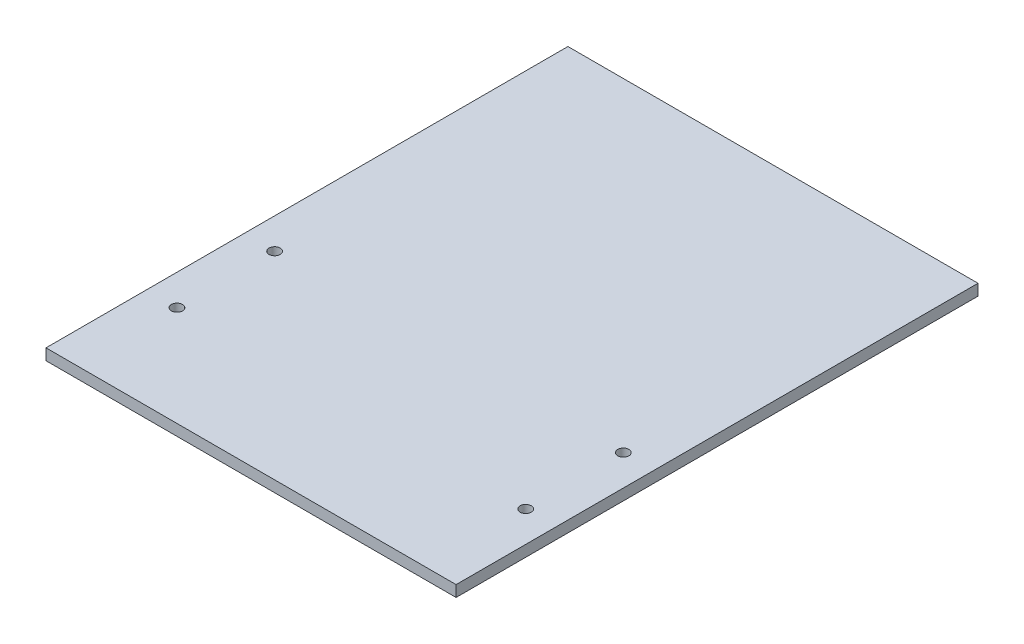
SolidWorks part; units mm, degrees
ref_plane "Front Plane" through (0, 0, 0) normal (0, 0, 1) x (1, 0, 0)
ref_plane "Top Plane" through (0, 0, 0) normal (0, 1, 0) x (1, 0, 0)
ref_plane "Right Plane" through (0, 0, 0) normal (1, 0, 0) x (0, 0, -1)
sketch "Sketch1" plane through (0, 0, 0) normal (0, 1, 0) x (1, 0, 0)
  line L1 (-55, -70) -> (55, -70)
  line L2 (-55, -70) -> (-55, 70)
  line L3 (-55, 70) -> (55, 70)
  line L4 (55, -70) -> (55, 70)
  line L5 (-55, -70) -> (55, 70) construction
  line L6 (-55, 70) -> (55, -70) construction
  point P0 (0, 0)
  dimension "D1" = 110
  dimension "D2" = 140
extrude "Boss-Extrude1" add sketch "Sketch1" along normal blind 3
sketch "Sketch2" plane through (0, 3, 0) normal (0, 1, 0) x (1, 0, 0)
  line L0 (-55, -30) -> (55, -30) construction
  line L1 (-55, 70) -> (-55, -70) construction
  line L2 (55, -70) -> (55, 70) construction
  line L3 (-46.7702, -6.2507) -> (-46.7702, -62.0916) construction
  line L4 (0, 70) -> (0, -70) construction
  line L5 (55, 70) -> (-55, 70) construction
  line L6 (-55, -70) -> (55, -70) construction
  line L7 (46.7702, -6.2507) -> (46.7702, -62.0916) construction
  circle A0 centre (-46.7702, -16.9) radius 1.5
  circle A1 centre (-46.7702, -43.1) radius 1.5
  circle A2 centre (46.7702, -43.1) radius 1.5
  circle A3 centre (46.7702, -16.9) radius 1.5
  dimension "D3" = 3
  dimension "D4" = 3
  dimension "D1" = 13.1
  dimension "D2" = 13.1
  dimension "D5" = 40
extrude "Cut-Extrude1" cut sketch "Sketch2" against normal through all
